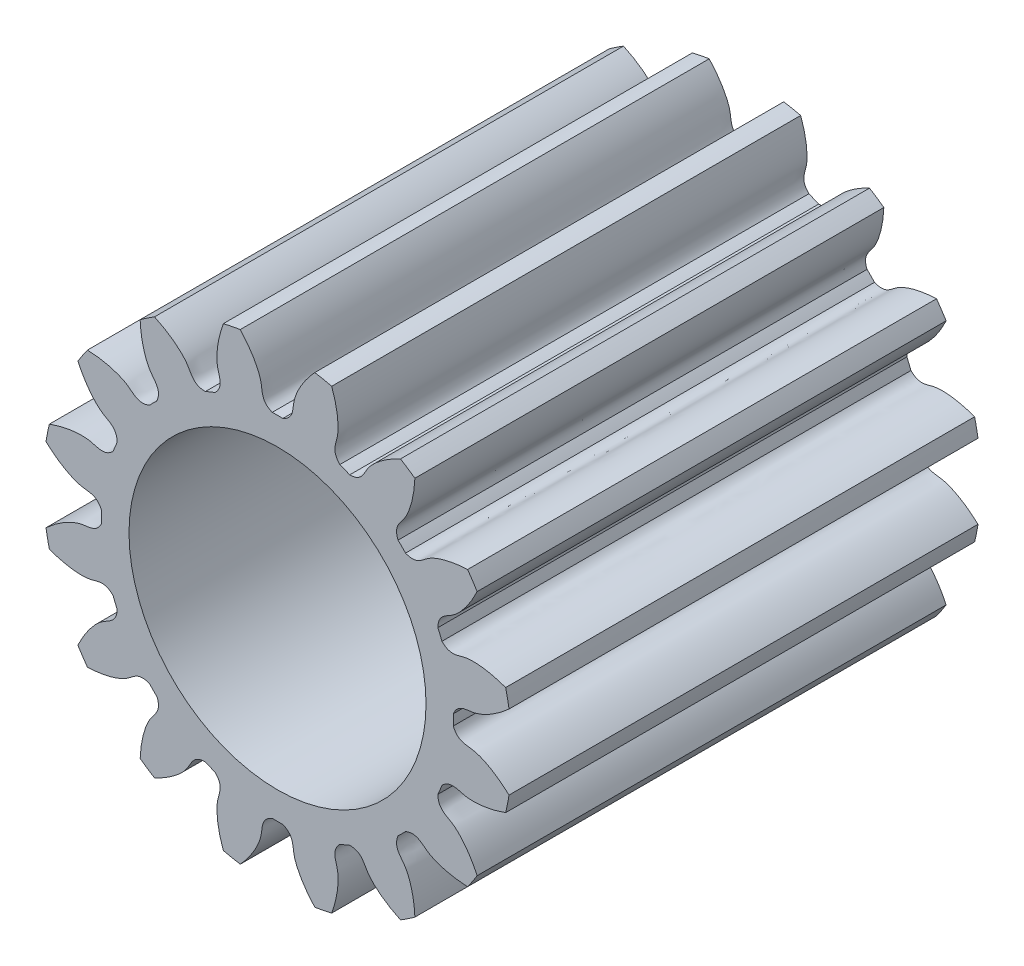
SolidWorks part; units mm, degrees
ref_plane "前视基准面" through (0, 0, 0) normal (0, 0, 1) x (1, 0, 0)
ref_plane "上视基准面" through (0, 0, 0) normal (0, 1, 0) x (1, 0, 0)
ref_plane "右视基准面" through (0, 0, 0) normal (1, 0, 0) x (0, 0, -1)
other "Configuration Table"
sketch "草图1" plane through (0, 0, 0) normal (0, 0, 1) x (1, 0, 0)
  circle A0 centre (0, 0) radius 4.5
extrude "凸台-拉伸1" add sketch "草图1" along normal blind 9
ref_axis "基准轴1" through (0, 0, 9) along (0, 0, -1)
sketch "草图2" plane through (0, 0, 0) normal (0, 0, 1) x (1, 0, 0)
  line L0 (0, 0) -> (0, 4.5) construction
  circle A0 centre (0, 0) radius 4.5 construction
  arc A1 (0.1017, 3.3735) -> (-0.1017, 3.3735) centre (0, 0) ccw
  arc A2 (1.5609, 5.0814) -> (-1.5609, 5.0814) centre (0, 0) ccw
  spline S0 degree 3 poles (0.1017, 3.3735) (0.3209, 3.4651) (0.2847, 3.6353) (0.3224, 3.7934) (0.3256, 3.8058) (0.3295, 3.8195) (0.334, 3.8346) (0.3394, 3.8511) (0.3455, 3.8688) (0.3526, 3.8879) (0.3605, 3.9082) (0.3695, 3.9297) (0.3794, 3.9524) (0.3905, 3.9763) (0.4027, 4.0013) (0.4161, 4.0274) (0.4307, 4.0545) (0.4466, 4.0827) (0.4638, 4.1118) (0.4823, 4.1419) (0.5023, 4.1728) (0.5238, 4.2046) (0.5467, 4.2372) (0.5712, 4.2705) (0.5973, 4.3045) (0.6249, 4.3392) (0.6543, 4.3744) (0.6853, 4.4102) (0.718, 4.4465) (0.7524, 4.4833) (0.7887, 4.5204) (0.8267, 4.5578) (0.8666, 4.5955) (0.9084, 4.6334) (0.952, 4.6715) (0.9975, 4.7096) (1.045, 4.7478) (1.0944, 4.7859) (1.1457, 4.8239) (1.1991, 4.8618) (1.2544, 4.8994) (1.3117, 4.9367) (1.3711, 4.9737) (1.4537, 5.023) (1.5175, 5.0584) (1.5609, 5.0814) knots 0 0 0 0 0.200958 0.205848 0.21139 0.217584 0.224431 0.231929 0.240079 0.248881 0.258335 0.268441 0.2792 0.29061 0.302672 0.315386 0.328753 0.342771 0.357441 0.372764 0.388738 0.405364 0.422643 0.440573 0.459155 0.47839 0.498276 0.518814 0.540005 0.561847 0.584342 0.607488 0.631287 0.655737 0.68084 0.706594 0.733001 0.760059 0.78777 0.816132 0.845147 0.874814 0.905132 0.936103 1 1 1 1
  spline S1 degree 3 poles (-0.1017, 3.3735) (-0.3209, 3.4651) (-0.2847, 3.6353) (-0.3224, 3.7934) (-0.3256, 3.8058) (-0.3295, 3.8195) (-0.334, 3.8346) (-0.3394, 3.8511) (-0.3455, 3.8688) (-0.3526, 3.8879) (-0.3605, 3.9082) (-0.3695, 3.9297) (-0.3794, 3.9524) (-0.3905, 3.9763) (-0.4027, 4.0013) (-0.4161, 4.0274) (-0.4307, 4.0545) (-0.4466, 4.0827) (-0.4638, 4.1118) (-0.4823, 4.1419) (-0.5023, 4.1728) (-0.5238, 4.2046) (-0.5467, 4.2372) (-0.5712, 4.2705) (-0.5973, 4.3045) (-0.6249, 4.3392) (-0.6543, 4.3744) (-0.6853, 4.4102) (-0.718, 4.4465) (-0.7524, 4.4833) (-0.7887, 4.5204) (-0.8267, 4.5578) (-0.8666, 4.5955) (-0.9084, 4.6334) (-0.952, 4.6715) (-0.9975, 4.7096) (-1.045, 4.7478) (-1.0944, 4.7859) (-1.1457, 4.8239) (-1.1991, 4.8618) (-1.2544, 4.8994) (-1.3117, 4.9367) (-1.3711, 4.9737) (-1.4537, 5.023) (-1.5175, 5.0584) (-1.5609, 5.0814) knots 0 0 0 0 0.200958 0.205848 0.21139 0.217584 0.224431 0.231929 0.240079 0.248881 0.258335 0.268441 0.2792 0.29061 0.302672 0.315386 0.328753 0.342771 0.357441 0.372764 0.388738 0.405364 0.422643 0.440573 0.459155 0.47839 0.498276 0.518814 0.540005 0.561847 0.584342 0.607488 0.631287 0.655737 0.68084 0.706594 0.733001 0.760059 0.78777 0.816132 0.845147 0.874814 0.905132 0.936103 1 1 1 1
extrude "切除-拉伸1" cut sketch "草图2" along normal through all
pattern_circular "阵列(圆周)1" count 16 every 22.5 about axis through (0, 0, 9) along (0, 0, -1) of "切除-拉伸1"
sketch "草图3" plane through (0, 0, 0) normal (0, 0, 1) x (1, 0, 0)
  circle A0 centre (0, 0) radius 4 construction
  dimension "Dn" = 8
sketch "草图4" plane through (0, 0, 9) normal (0, 0, 1) x (1, 0, 0)
  circle A0 centre (0, 0) radius 2.85
  dimension "D1" = 5.7
extrude "切除-拉伸2" cut sketch "草图4" against normal blind 10
